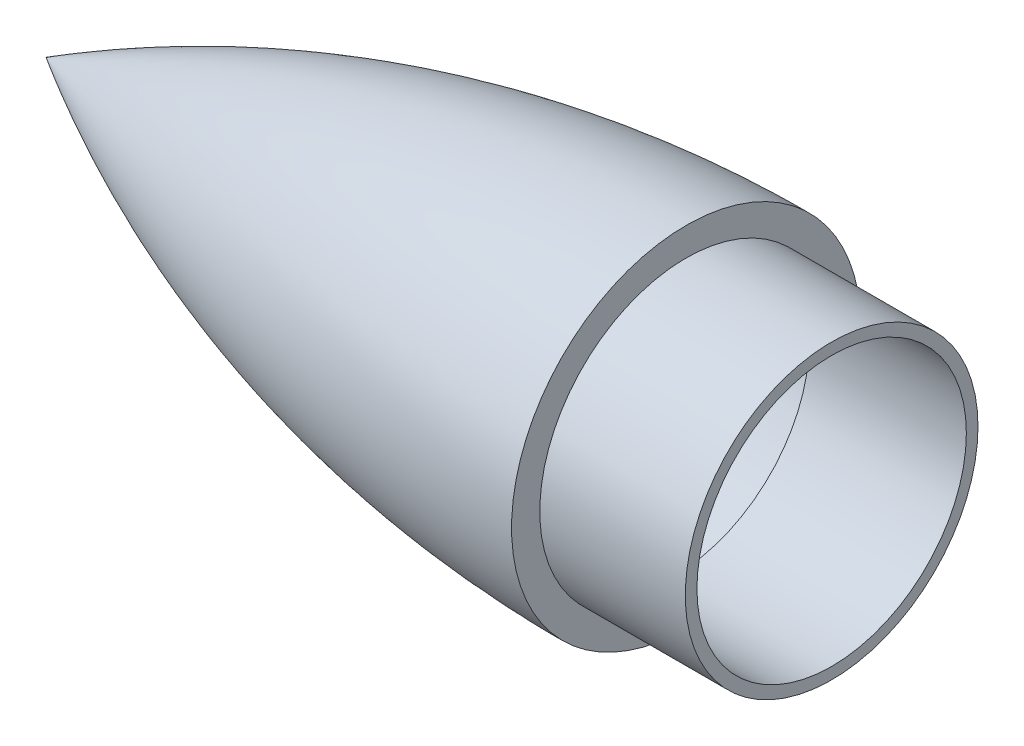
SolidWorks part; units mm, degrees
ref_plane "Front Plane" through (0, 0, 0) normal (0, 0, 1) x (1, 0, 0)
ref_plane "Top Plane" through (0, 0, 0) normal (0, 1, 0) x (1, 0, 0)
ref_plane "Right Plane" through (0, 0, 0) normal (1, 0, 0) x (0, 0, -1)
sketch "Sketch2" plane through (0, 0, 0) normal (0, 0, 1) x (1, 0, 0)
  line L0 (0, 216.6666) -> (0, 186.6666)
  line L3 (0, 186.6666) -> (-110, 186.6666)
  arc A1 (0, 216.6666) -> (-110, 186.6666) centre (0, 0) ccw
  point P1 (0, 216.6666)
  point P4 (0, 186.6666)
  dimension "D1" = 30
  dimension "D2" = 110
revolve "Revolve2" add sketch "Sketch2" angle 360 about L3
sketch "Sketch4" plane through (0, 0, 0) normal (1, 0, 0) x (0, 0, -1)
  circle A0 centre (0, 186.6666) radius 25.15
  dimension "D1" = 50.3
extrude "Boss-Extrude2" add sketch "Sketch4" along normal blind 25 contours A0
shell "Shell2" thickness 2 removed face at (25, 186.6666, -25.15)
sketch "Sketch5" plane through (25, 0, 0) normal (1, 0, 0) x (0, 0, -1)
  circle A0 centre (0, 210.6717) radius 1
  circle A1 centre (0, 162.7706) radius 1
  point P1 (0, 210.6717)
  point P2 (0, 162.7706)
  dimension "D1" = 2
